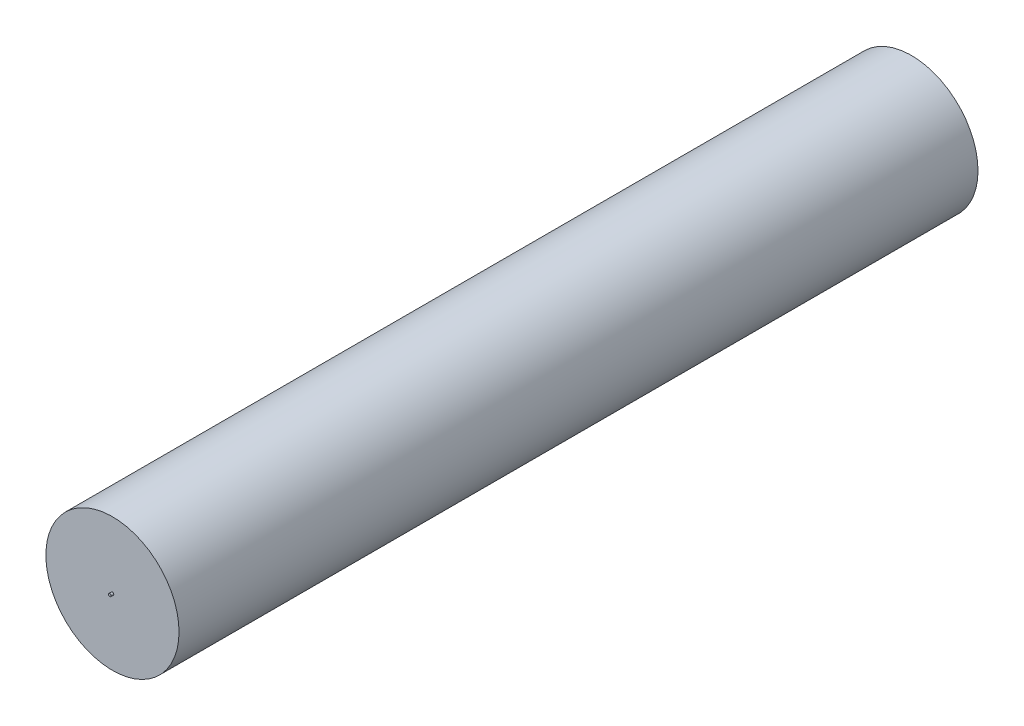
SolidWorks part; units mm, degrees
ref_plane "Front Plane" through (0, 0, 0) normal (0, 0, 1) x (1, 0, 0)
ref_plane "Top Plane" through (0, 0, 0) normal (0, 1, 0) x (1, 0, 0)
ref_plane "Right Plane" through (0, 0, 0) normal (1, 0, 0) x (0, 0, -1)
sketch "Sketch1" plane through (0, 0, 0) normal (0, 0, 1) x (1, 0, 0)
  circle A0 centre (0, 0) radius 25
  dimension "D1" = 50
extrude "Boss-Extrude1" add sketch "Sketch1" along normal blind 150 and the other way blind 150
sketch "Sketch2" plane through (0, 0, 150) normal (0, 0, 1) x (1, 0, 0)
  circle A0 centre (0, 0) radius 0.5
  dimension "D1" = 1
extrude "Boss-Extrude2" add sketch "Sketch2" along normal blind 1
